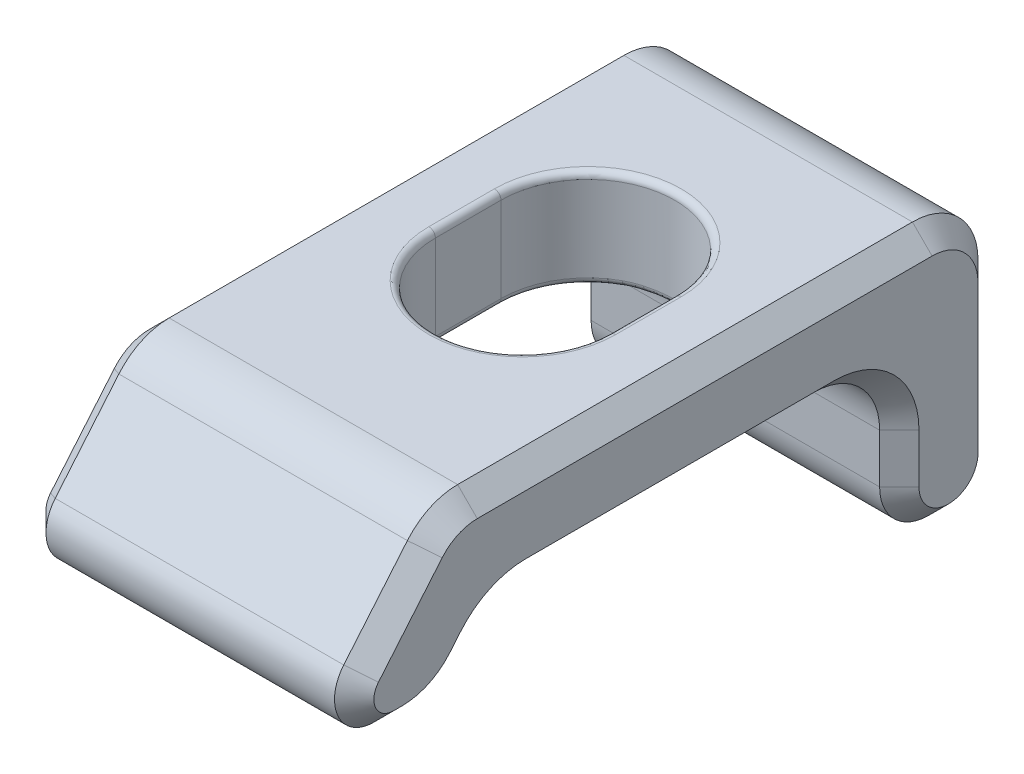
SolidWorks part; units mm, degrees
ref_plane "Front Plane" through (0, 0, 0) normal (0, 0, 1) x (1, 0, 0)
ref_plane "Top Plane" through (0, 0, 0) normal (0, 1, 0) x (1, 0, 0)
ref_plane "Right Plane" through (0, 0, 0) normal (1, 0, 0) x (0, 0, -1)
sketch "Sketch1" plane through (0, 0, 0) normal (1, 0, 0) x (0, 0, -1)
  line L0 (0, 0) -> (0, 8)
  line L1 (0, 8) -> (-16.8045, 8)
  line L2 (-16.8045, 8) -> (-21, 3)
  line L3 (-21, 3) -> (-17, 3)
  line L4 (-17, 3) -> (-15.3218, 5)
  line L5 (-15.3218, 5) -> (-3, 5)
  line L6 (-3, 5) -> (-3, 0)
  line L7 (-3, 0) -> (0, 0)
  dimension "D1" = 8
  dimension "D2" = 21
  dimension "D3" = 3
  dimension "D4" = 3
  dimension "D5" = 130
  dimension "D6" = 2
  dimension "D7" = 4
  dimension "D8" = 3
extrude "Boss-Extrude1" add sketch "Sketch1" along normal blind 10
sketch "Sketch2" plane through (0, 8, 0) normal (0, 1, 0) x (1, 0, 0)
  line L0 (5, -7.5) -> (5, -9.5) construction
  line L1 (7.65, -7.5) -> (7.65, -9.5)
  line L2 (2.35, -7.5) -> (2.35, -9.5)
  line L3 (5, -7.5) -> (5, 0) construction
  line L4 (10, 0) -> (0, 0) construction
  arc A0 (7.65, -7.5) -> (2.35, -7.5) centre (5, -7.5) ccw
  arc A1 (2.35, -9.5) -> (7.65, -9.5) centre (5, -9.5) ccw
  point P2 (5, -8.5)
  dimension "D1" = 2.65
  dimension "D2" = 2
  dimension "D3" = 8.5
extrude "Cut-Extrude1" cut sketch "Sketch2" against normal through all
fillet "Fillet1" radius 1.5 2 edges at (5, 0, 0) (5, 0, 3)
fillet "Fillet2" radius 1.2 1 edges at (5, 3, 21)
fillet "Fillet3" radius 2.5 1 edges at (5, 3, 17)
fillet "Fillet4" radius 2 4 edges at (5, 8, 16.8045) (5, 8, 0) (5, 5, 3) (5, 5, 15.3218)
chamfer "Chamfer1" distance 0.6 angle 45 30 edges at (0, 3.6929, 19.5142) (0, 3, 18.2962) (0, 3.2342, 17.1092) (0, 4.0893, 16.086) (0, 4.8126, 15.2344) (0, 5, 9.6946) (0, 4.4142, 3.5858) (0, 2.25, 3) (0, 0.4393, 2.5607) (0, 0.4393, 0.4393) (0, 3.75, 0) (0, 7.4142, 0.5858) (0, 8, 8.9359) (0, 7.8126, 16.7171) (0, 6.1285, 18.3749) (10, 7.4142, 0.5858) (10, 3.75, 0) (10, 0.4393, 0.4393) (10, 0.4393, 2.5607) (10, 2.25, 3) (10, 4.4142, 3.5858) (10, 5, 9.6946) (10, 4.8126, 15.2344) (10, 4.0893, 16.086) (10, 3.2342, 17.1092) (10, 3, 18.2962) (10, 3.6929, 19.5142) (10, 6.1285, 18.3749) (10, 7.8126, 16.7171) (10, 8, 8.9359)
fillet "Fillet5" radius 0.2 10 edges at (7.65, 8, 8.5) (5, 8, 12.15) (2.35, 8, 8.5) (7.65, 5, 8.5) (5, 5, 12.15) (2.35, 5, 8.5) (5, 8, 4.85) (2.8376, 5, 5.9681) (7.1624, 5, 5.9681) (5, 5, 4.85)
equation "\"D1@Sketch2\"=5.3/2"
